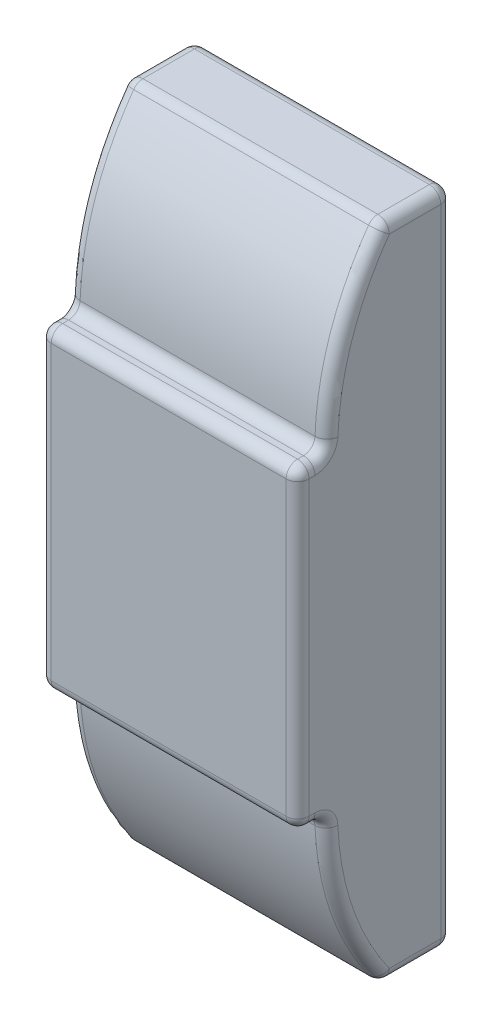
SolidWorks part; units mm, degrees
material "ABS"
ref_plane "Plan de face" through (0, 0, 0) normal (0, 0, 1) x (1, 0, 0)
ref_plane "Plan de dessus" through (0, 0, 0) normal (0, 1, 0) x (1, 0, 0)
ref_plane "Plan de droite" through (0, 0, 0) normal (1, 0, 0) x (0, 0, -1)
sketch "Esquisse1" plane through (0, 0, 0) normal (0, 0, 1) x (1, 0, 0)
  line L1 (-22.5, 57.5) -> (22.5, 57.5)
  line L2 (-22.5, 57.5) -> (-22.5, -57.5)
  line L3 (-22.5, -57.5) -> (22.5, -57.5)
  line L4 (22.5, 57.5) -> (22.5, -57.5)
  line L5 (-22.5, 57.5) -> (22.5, -57.5) construction
  line L6 (-22.5, -57.5) -> (22.5, 57.5) construction
  point P0 (0, 0)
  dimension "D1" = 115
  dimension "D2" = 45
extrude "Boss.-Extru.1" add sketch "Esquisse1" along normal blind 27
sketch "Esquisse2" plane through (-22.5, 0, 0) normal (-1, 0, 0) x (0, 0, 1)
  line L0 (30.8718, 27.5) -> (22, 27.5)
  line L1 (27, 57.5) -> (0, 57.5) construction
  line L2 (12, 57.5) -> (30.8718, 57.5)
  line L3 (30.8718, 57.5) -> (30.8718, 27.5)
  line L4 (27, 57.5) -> (27, -57.5) construction
  arc A0 (22, 27.5) -> (12, 57.5) centre (-28, 27.5) ccw
  dimension "D1" = 5
  dimension "D3" = 50
  dimension "D2" = 15
  dimension "D4" = 30
extrude "Enlèv. mat.-Extru.1" cut sketch "Esquisse2" against normal through all
mirror "Symétrie1" about plane through (0, 0, 0) normal (0, 1, 0) of "Enlèv. mat.-Extru.1"
fillet "Congé1" radius 2 24 edges at (22.5, -27.5, 24.5) (22.5, 27.5, 24.5) (22.5, 0, 0) (0, 57.5, 0) (22.5, 57.5, 6) (0, 57.5, 12) (22.5, 43.3114, 19.4342) (0, 27.5, 22) (22.5, -57.5, 6) (0, -57.5, 0) (-22.5, -57.5, 6) (-22.5, 0, 0) (-22.5, 57.5, 6) (-22.5, 43.3114, 19.4342) (-22.5, 27.5, 24.5) (-22.5, -27.5, 24.5) (0, -27.5, 22) (22.5, -43.3114, 19.4342) (0, -57.5, 12) (-22.5, -43.3114, 19.4342) (0, 27.5, 27) (22.5, 0, 27) (0, -27.5, 27) (-22.5, 0, 27)
